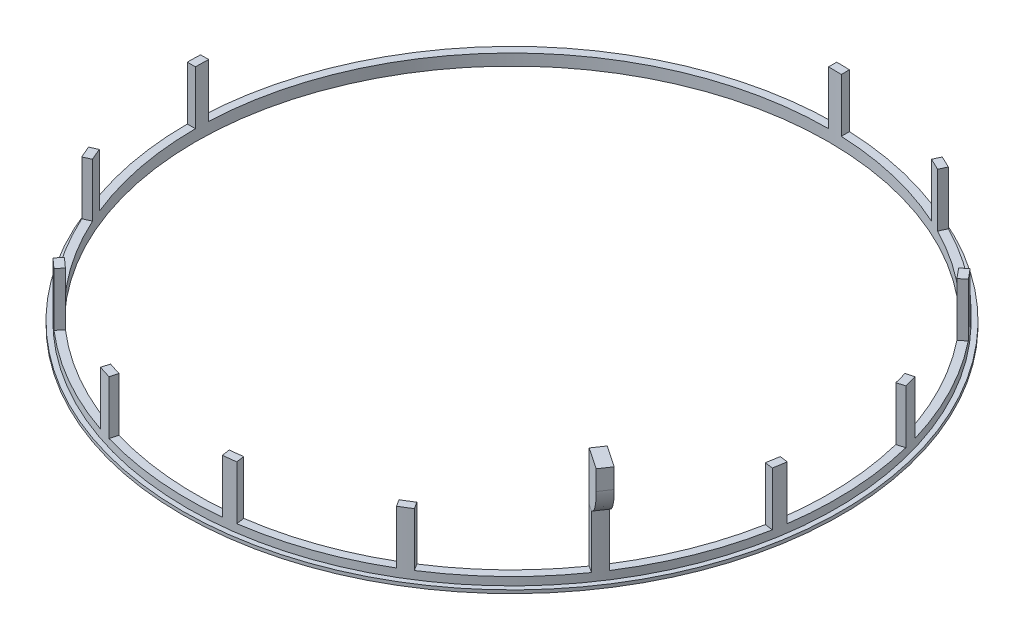
SolidWorks part; units mm, degrees
ref_plane "Front Plane" through (0, 0, 0) normal (0, 0, 1) x (1, 0, 0)
ref_plane "Top Plane" through (0, 0, 0) normal (0, 1, 0) x (1, 0, 0)
ref_plane "Right Plane" through (0, 0, 0) normal (1, 0, 0) x (0, 0, -1)
sketch "Sketch1" plane through (0, 0, 0) normal (0, 1, 0) x (1, 0, 0)
  line L0 (0, 0) -> (-101.5, 0)
  line L1 (0, 4) -> (-101.4212, 4)
  circle A0 centre (0, 0) radius 100
  circle A1 centre (0, 0) radius 97.5
  circle A2 centre (0, 0) radius 101.5
  dimension "D1" = 200
  dimension "D2" = 195
  dimension "D3" = 4
  dimension "D4" = 203
extrude "Boss-Extrude1" add sketch "Sketch1" along normal blind 3.5 contours A0 A1 | A1 L1 A0 L0 region at (0, 0, 97.7828) region at (-98.723, 0, -2.0003)
extrude "Boss-Extrude2" add sketch "Sketch1<3>" along normal blind 1 contours A2 A0 | L1 A2 L0 A0 region at (0, 0, 100.2871) region at (-100.7235, 0, -2.0003)
sketch "Sketch1<3>" plane through (0, 0, 0) normal (0, 1, 0) x (1, 0, 0) same geometry as "Sketch1"
extrude "Boss-Extrude3" add sketch "Sketch1<4>" along normal blind 20 contours A1 L1 A0 L0 region at (-98.723, 0, -2.0003)
sketch "Sketch1<4>" plane through (0, 0, 0) normal (0, 1, 0) x (1, 0, 0) same geometry as "Sketch1"
pattern_circular "CirPattern1" count 12 every 24.545 about axis through (0, 3.5, 0) along (0, 1, 0) of "Boss-Extrude3"
sketch "Sketch3" plane through (0, 20, 0) normal (0, 1, 0) x (1, 0, 0)
  line L0 (82.0222, -52.7125) -> (79.7906, -56.0331)
  line L5 (82.0222, -52.7125) -> (88.6621, -57.1748)
  line L6 (79.7906, -56.0331) -> (86.4305, -60.4954)
  line L7 (86.4305, -60.4954) -> (88.6621, -57.1748)
  dimension "D1" = 8
extrude "Boss-Extrude4" add sketch "Sketch3" along normal offset from surface (15 mm away) 35 up to face at (0, 0, 97.5)
fillet "Fillet1" radius 10 1 edges at (87.5463, 20, 58.8351)
